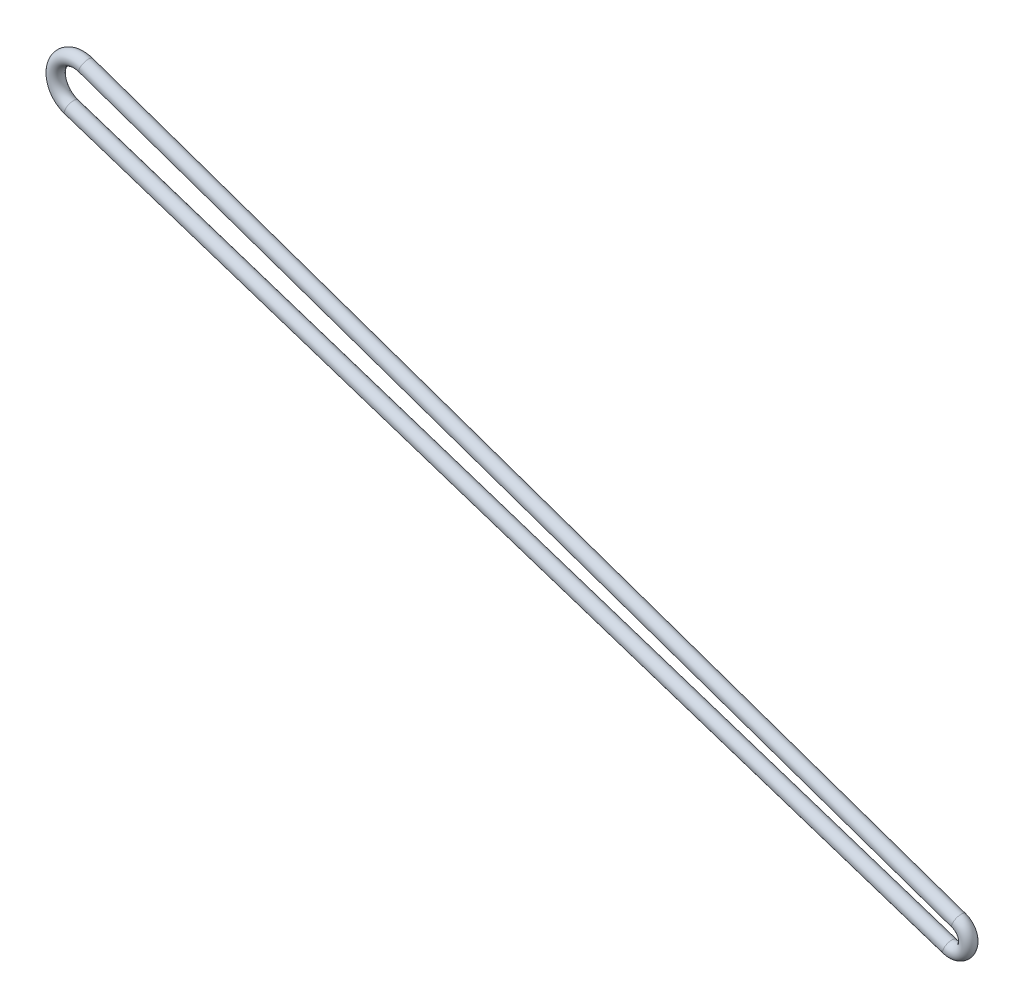
SolidWorks part; units mm, degrees
ref_plane "前视基准面" through (0, 0, 0) normal (0, 0, 1) x (1, 0, 0)
ref_plane "上视基准面" through (0, 0, 0) normal (0, 1, 0) x (1, 0, 0)
ref_plane "右视基准面" through (0, 0, 0) normal (1, 0, 0) x (0, 0, -1)
sketch "草图2" plane through (0, 0, 0) normal (0, 0, 1) x (1, 0, 0)
  line L0 (0, 0) -> (1, 0) construction
  line L1 (0, 0) -> (0, 1) construction
  line L2 (316.6806, 89.1401) -> (124.4612, 152.1023)
  line L3 (127.663, 161.5754) -> (318.6657, 95.0134)
  arc A0 (318.6657, 95.0134) -> (316.6806, 89.1401) centre (317.6456, 92.0861) cw
  arc A1 (124.4612, 152.1023) -> (127.663, 161.5754) centre (126.0176, 156.8539) cw
sweep "扫描19" add path "草图2" circular profile diameter 3 parameters "D3"=3
